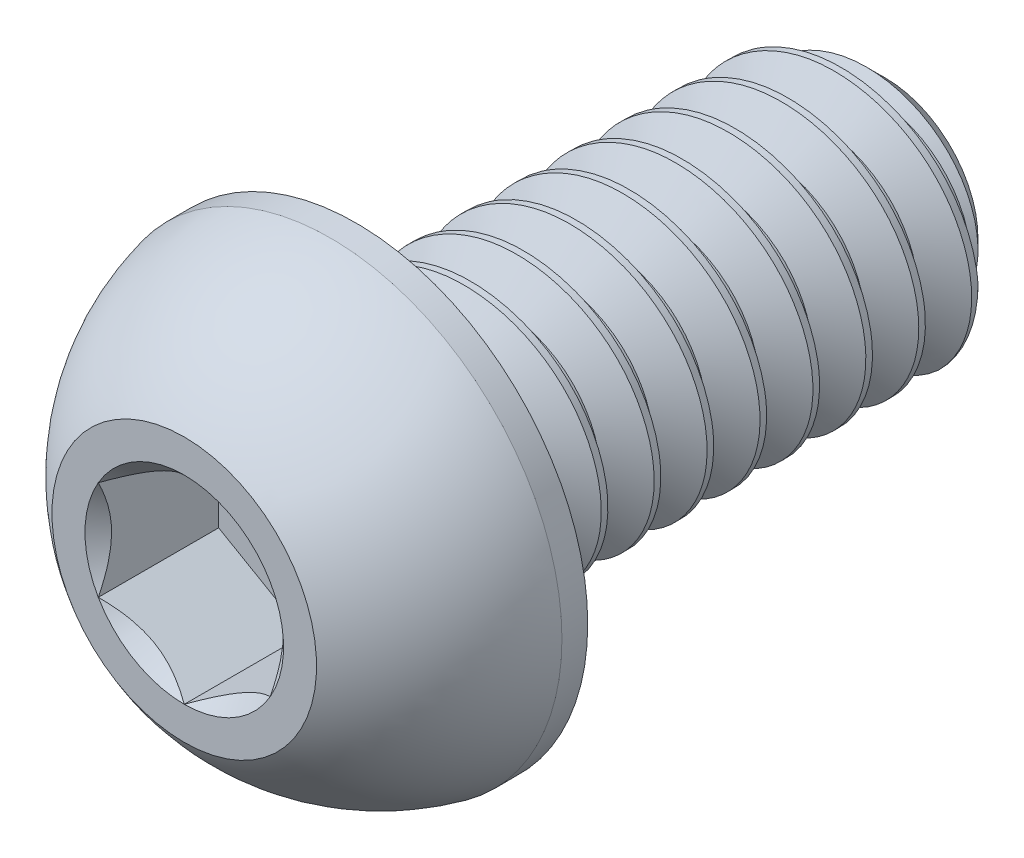
SolidWorks part; units mm, degrees
material "Passivated 18-8 Stainless Steel"
ref_plane "Front" through (0, 0, 0) normal (0, 0, 1) x (1, 0, 0)
ref_plane "Top" through (0, 0, 0) normal (0, 1, 0) x (1, 0, 0)
ref_plane "Right" through (0, 0, 0) normal (1, 0, 0) x (0, 0, -1)
sketch "Sketch1" plane through (0, 0, 0) normal (1, 0, 0) x (0, 0, -1)
  line L2 (1.3, 1) -> (5.3, 1)
  line L3 (5.3, 1) -> (5.3, 0)
  line L4 (5.3, 0) -> (1.3, 0)
  line L6 (1.105, 1.75) -> (1.3, 1.75) construction
  line L7 (5.3, 1) -> (5.3, -1) construction
  line L8 (0, 0) -> (1.3, 0) construction
  line L9 (1.3, 1.75) -> (1.3, -1.75) construction
  line L11 (1.3, 1) -> (1.3, 0)
  line L13 (0, 0.65) -> (0, -0.65) construction
  line L14 (0, 0.65) -> (0, 1) construction
  arc A3 (0, 1) -> (1.105, 1.75) centre (1.4858, 0) cw construction
  dimension "D1" = 0.195
revolve "Revolve1" add sketch "Sketch1" angle 360 mid plane about L4
sketch "Sketch3" plane through (0, 0, -5.3) normal (0, 0, -1) x (-1, 0, 0)
  circle A0 centre (0, 0) radius 1
curve "Helix/Spiral1" pitch 0.4 height 4.4 radius 1 centre (0, 0, -5.3) axis (0, 0, 1) start towards (0, 1, 0)
sketch "Sketch2" plane through (0, 0, 0) normal (1, 0, 0) x (0, 0, -1)
  line L0 (5.3, 1) -> (5.65, 1)
  line L1 (5.65, 1) -> (5.5, 0.7402)
  line L2 (5.5, 0.7402) -> (5.45, 0.7402)
  line L3 (5.45, 0.7402) -> (5.3, 1)
  line L4 (5.375, 0.8701) -> (5.575, 0.8701) construction
  dimension "D1" = 60
  dimension "D2" = 0.05
  dimension "D3" = 0.2
chamfer "Chamfer1" distance 0.3 angle 45 1 edges at (0, 1, -5.3)
sweep "Cut-Sweep1" cut profiles "Sketch2" path "Helix/Spiral1" align with end faces yes
sketch "Sketch7" plane through (0, 0, 0) normal (1, 0, 0) x (0, 0, -1)
  line L6 (1.105, 1.75) -> (1.3, 1.75) construction
  line L8 (0, 0) -> (1.3, 0) construction
  line L11 (1.3, 1.75) -> (1.3, -1.75) construction
  line L12 (1.105, 1.75) -> (1.3, 1.75)
  line L13 (0, 0) -> (1.3, 0)
  line L14 (0, 0.65) -> (0, -0.65) construction
  line L15 (1.3, 1.75) -> (1.3, 0)
  line L16 (0, 1) -> (0, 0)
  arc A2 (1.105, 1.75) -> (0, 1) centre (1.4858, 0) ccw construction
  arc A3 (1.105, 1.75) -> (0, 1) centre (1.4858, 0) ccw
revolve "Revolve2" add sketch "Sketch7" angle 360 mid plane about L13
sketch "Sketch5" plane through (0, 0, 0) normal (0, 0, 1) x (1, 0, 0)
  line L1 (0.65, -0.3753) -> (0.65, 0.3753)
  line L2 (0.65, 0.3753) -> (0, 0.7506)
  line L3 (0, 0.7506) -> (-0.65, 0.3753)
  line L4 (-0.65, 0.3753) -> (-0.65, -0.3753)
  line L5 (-0.65, -0.3753) -> (0, -0.7506)
  line L6 (0, -0.7506) -> (0.65, -0.3753)
  circle A0 centre (0, 0) radius 0.65 construction
extrude "Cut-Extrude2" cut sketch "Sketch5" against normal blind 0.91
sketch "Sketch6" plane through (0, 0, 0) normal (0, 0, 1) x (1, 0, 0)
  circle A0 centre (0, 0) radius 0.7506
extrude "Cut-Extrude3" cut sketch "Sketch6" against normal blind 0.91 draft 45
sketch "Sketch9" [suppressed] plane through (0, 0, -4.2164) normal (0, 0, 1) x (1, 0, 0)
  circle A2 centre (0, 0) radius 3.9687
extrude "Boss-Extrude2" [suppressed] add sketch "Sketch9" against normal offset from surface (9.525 mm away) 28.575 up to face at (0, 0.7, -5.3)
sketch "Sketch10" plane through (0, 0, 0) normal (1, 0, 0) x (0, 0, -1)
  line L0 (5.3, 1) -> (5.3, -1) construction
  point P0 (4.7, -1)
  dimension "D1" = 0.6
equation "\"D3@Helix/Spiral1\" = \"Lg@Sketch1\" + \"D4@Helix/Spiral1\""
equation "\"D2@Sketch2\" = \"D4@Helix/Spiral1\" * .125"
equation "\"D3@Sketch2\" = \"D4@Helix/Spiral1\" * .5"
equation "\"D1@Chamfer1\" = \"D4@Helix/Spiral1\" * .75"
equation "\"D1@Cut-Extrude2\" = \"Head Ht@Sketch1\" * .7"
equation "\"D1@Sketch1\" = \"Head Ht@Sketch1\" * .15"
equation "\"D1@Sketch10\" = \"D4@Helix/Spiral1\" * 1.5"
equation "\"D1@Cut-Extrude3\" = \"D1@Cut-Extrude2\""
